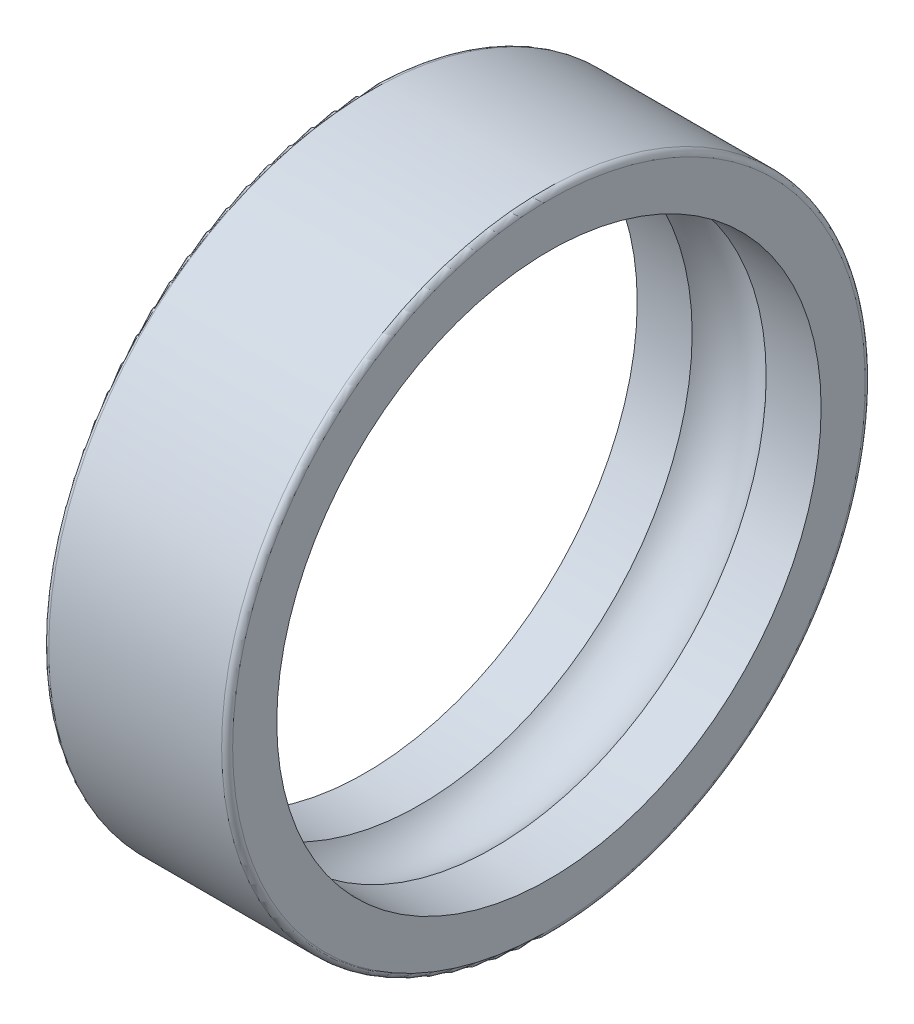
SolidWorks part; units mm, degrees
ref_plane "Plan1" through (0, 0, 0) normal (0, 0, 1) x (1, 0, 0)
ref_plane "Plan2" through (0, 0, 0) normal (0, 1, 0) x (1, 0, 0)
ref_plane "Plan3" through (0, 0, 0) normal (1, 0, 0) x (0, 0, -1)
ref_axis "Axe1" through (-50, 0, 0) along (1, 0, 0)
sketch "Esquisse1" plane through (0, 0, 0) normal (0, 1, 0) x (1, 0, 0)
  line L0 (0, 17.2) -> (0, 8.8) construction
  line L1 (10, 14.8) -> (0, 14.8) construction
  line L2 (10, 17.2) -> (10, 8.8) construction
  line L3 (0.3, 17.5) -> (9.7, 17.5) construction
  line L4 (0, 17.2) -> (0, 14.8)
  line L5 (10, 14.8) -> (7.0125, 14.8)
  line L6 (0, 0) -> (12, 0) construction
  line L7 (-50, 0) -> (200, 0) construction
  line L8 (10, 17.2) -> (10, 14.8)
  line L9 (0.3, 17.5) -> (9.7, 17.5)
  line L10 (2.9875, 14.8) -> (0, 14.8)
  arc A0 (0.3, 17.5) -> (0, 17.2) centre (0.3, 17.2) ccw construction
  circle A1 centre (5, 13) radius 2.7 construction
  arc A3 (10, 17.2) -> (9.7, 17.5) centre (9.7, 17.2) ccw construction
  arc A4 (0.3, 17.5) -> (0, 17.2) centre (0.3, 17.2) ccw
  arc A5 (7.0125, 14.8) -> (2.9875, 14.8) centre (5, 13) ccw
  arc A6 (10, 17.2) -> (9.7, 17.5) centre (9.7, 17.2) ccw
revolve "Base-Révolution" add sketch "Esquisse1" angle 360 about L6
